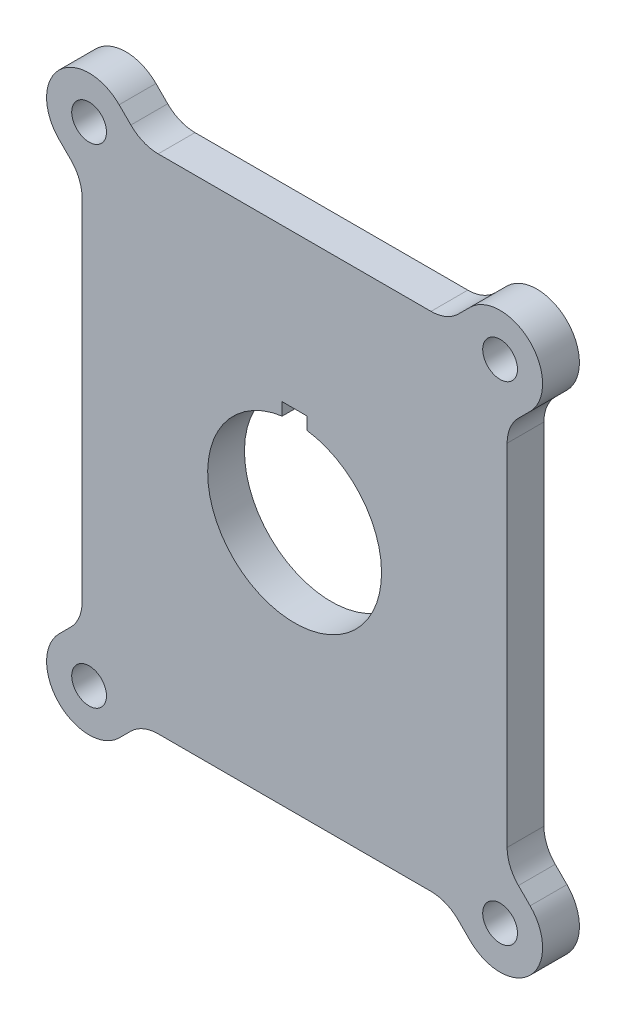
SolidWorks part; units mm, degrees
material "Acrylic (Medium-high impact)"
ref_plane "X-Y Datum" through (0, 0, 0) normal (0, 0, 1) x (1, 0, 0)
ref_plane "X-Z Datum" through (0, 0, 0) normal (0, 1, 0) x (1, 0, 0)
ref_plane "Y-Z Datum" through (0, 0, 0) normal (1, 0, 0) x (0, 0, -1)
sketch "Sketch4" plane through (0, 0, -59.6689) normal (0, 0, 1) x (1, 0, 0)
  line L0 (-30.7488, 16.211) -> (24.2512, 16.211) construction
  line L1 (-1.6488, 27.3466) -> (-1.6488, 28.961)
  line L2 (-4.8488, 27.3466) -> (-4.8488, 28.961)
  line L3 (-4.8488, 28.961) -> (-1.6488, 28.961)
  line L12 (14.402, 48.711) -> (-20.8995, 48.711)
  line L13 (-24.4351, 50.1754) -> (-25.951, 51.6914)
  line L14 (-33.7292, 43.9132) -> (-32.2132, 42.3973)
  line L15 (-30.7488, 38.8617) -> (-30.7488, -6.4398)
  line L16 (-32.2132, -9.9753) -> (-33.7292, -11.4913)
  line L17 (-25.951, -19.2695) -> (-24.4351, -17.7535)
  line L18 (-20.8995, -16.289) -> (14.402, -16.289)
  line L19 (17.9375, -17.7535) -> (19.4535, -19.2695)
  line L20 (27.2317, -11.4913) -> (25.7157, -9.9753)
  line L22 (25.7157, 42.3973) -> (27.2317, 43.9132)
  line L23 (19.4535, 51.6914) -> (17.9375, 50.1754)
  line L24 (14.402, 48.711) -> (-20.8995, 48.711)
  line L25 (-24.4351, 50.1754) -> (-25.951, 51.6914)
  line L26 (-33.7292, 43.9132) -> (-32.2132, 42.3973)
  line L28 (-32.2132, -9.9753) -> (-33.7292, -11.4913)
  line L29 (-25.951, -19.2695) -> (-24.4351, -17.7535)
  line L30 (-20.8995, -16.289) -> (14.402, -16.289)
  line L31 (17.9375, -17.7535) -> (19.4535, -19.2695)
  line L32 (27.2317, -11.4913) -> (25.7157, -9.9753)
  line L34 (25.7157, 42.3973) -> (27.2317, 43.9132)
  line L35 (19.4535, 51.6914) -> (17.9375, 50.1754)
  line L43 (-30.7488, 38.8617) -> (-30.7488, -6.4398)
  line L45 (24.2512, -6.4398) -> (24.2512, 38.8617)
  line L47 (24.2512, -6.4398) -> (24.2512, 38.8617)
  arc A1 (-4.8488, 27.3466) -> (-1.6488, 27.3466) centre (-3.2488, 16.211) ccw
  arc A4 (-25.951, 51.6914) -> (-33.7292, 43.9132) centre (-29.8401, 47.8023) ccw
  arc A5 (-33.7292, -11.4913) -> (-25.951, -19.2695) centre (-29.8401, -15.3804) ccw
  arc A6 (19.4535, -19.2695) -> (27.2317, -11.4913) centre (23.3426, -15.3804) ccw
  arc A7 (27.2317, 43.9132) -> (19.4535, 51.6914) centre (23.3426, 47.8023) ccw
  arc A8 (-25.951, 51.6914) -> (-33.7292, 43.9132) centre (-29.8401, 47.8023) ccw
  arc A9 (-33.7292, -11.4913) -> (-25.951, -19.2695) centre (-29.8401, -15.3804) ccw
  arc A10 (19.4535, -19.2695) -> (27.2317, -11.4913) centre (23.3426, -15.3804) ccw
  arc A11 (27.2317, 43.9132) -> (19.4535, 51.6914) centre (23.3426, 47.8023) ccw
  arc A34 (14.402, 48.711) -> (17.9375, 50.1754) centre (14.402, 53.711) ccw
  arc A35 (14.402, 48.711) -> (17.9375, 50.1754) centre (14.402, 53.711) ccw
  arc A36 (-24.4351, 50.1754) -> (-20.8995, 48.711) centre (-20.8995, 53.711) ccw
  arc A37 (-24.4351, 50.1754) -> (-20.8995, 48.711) centre (-20.8995, 53.711) ccw
  arc A38 (-30.7488, 38.8617) -> (-32.2132, 42.3973) centre (-35.7488, 38.8617) ccw
  arc A39 (-30.7488, 38.8617) -> (-32.2132, 42.3973) centre (-35.7488, 38.8617) ccw
  arc A40 (-32.2132, -9.9753) -> (-30.7488, -6.4398) centre (-35.7488, -6.4398) ccw
  arc A41 (-32.2132, -9.9753) -> (-30.7488, -6.4398) centre (-35.7488, -6.4398) ccw
  arc A42 (-20.8995, -16.289) -> (-24.4351, -17.7535) centre (-20.8995, -21.289) ccw
  arc A43 (-20.8995, -16.289) -> (-24.4351, -17.7535) centre (-20.8995, -21.289) ccw
  arc A44 (17.9375, -17.7535) -> (14.402, -16.289) centre (14.402, -21.289) ccw
  arc A45 (17.9375, -17.7535) -> (14.402, -16.289) centre (14.402, -21.289) ccw
  arc A46 (24.2512, -6.4398) -> (25.7157, -9.9753) centre (29.2512, -6.4398) ccw
  arc A47 (24.2512, -6.4398) -> (25.7157, -9.9753) centre (29.2512, -6.4398) ccw
  arc A48 (25.7157, 42.3973) -> (24.2512, 38.8617) centre (29.2512, 38.8617) ccw
  arc A49 (25.7157, 42.3973) -> (24.2512, 38.8617) centre (29.2512, 38.8617) ccw
  point P14 (-3.2488, 16.211)
  point P29 (-3.2488, 28.961)
  dimension "D2" = 22.5
  dimension "D3" = 3.2
  dimension "D4" = 1.6144
  dimension "D1" = 0
extrude "Boss-Extrude1" add sketch "Sketch4" along normal blind 4.7625
hole_wizard "M4 Clearance Hole2" positions "Sketch5" profile "Sketch6" hole size "M4" standard "ANSI Metric" end condition through all
sketch "Sketch5" plane through (0, 0, -54.9064) normal (0, 0, 1) x (1, 0, 0)
  point P0 (-29.8401, 47.8023)
  point P3 (23.3426, 47.8023)
  point P6 (23.3426, -15.3804)
  point P9 (-29.8401, -15.3804)
sketch "Sketch6" plane through (-29.8401, 47.8023, -54.9064) normal (1, 0, 0) x (0, -1, 0)
  line L0 (0, 0) -> (0, 4.7625)
  line L1 (0, 4.7625) -> (2.25, 4.7625)
  line L2 (2.25, 4.7625) -> (2.25, 0)
  line L5 (2.25, 0) -> (0, 0)
  line L11 (0, -6.35) -> (0, 107.95) construction
  dimension "Thru Hole Dia." = 4.5
  dimension "Thru Hole Depth" = 4.7625
